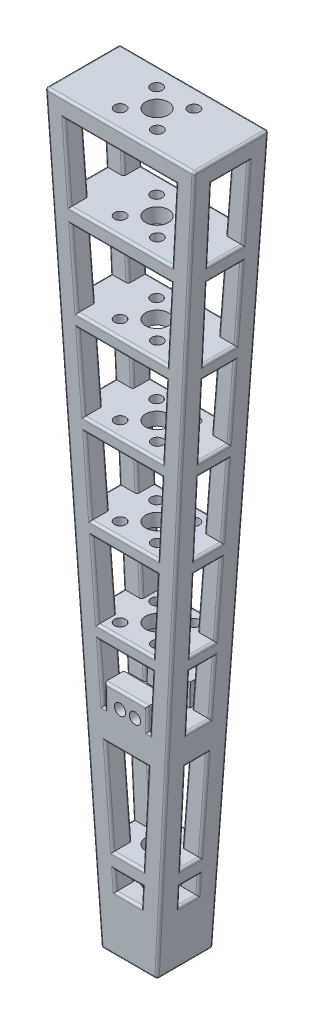
SolidWorks part; units mm, degrees
ref_plane "Płaszczyzna przednia" through (0, 0, 0) normal (0, 0, 1) x (1, 0, 0)
ref_plane "Płaszczyzna górna" through (0, 0, 0) normal (0, 1, 0) x (1, 0, 0)
ref_plane "Płaszczyzna prawa" through (0, 0, 0) normal (1, 0, 0) x (0, 0, -1)
sketch "Szkic1" plane through (0, 0, 0) normal (0, 0, 1) x (1, 0, 0)
  line L0 (0, 0) -> (-15, 0)
  line L1 (-15, 0) -> (-27.5076, 195)
  line L2 (-27.5076, 195) -> (12.4924, 195)
  line L3 (12.4924, 195) -> (0, 0)
  dimension "D1" = 15
  dimension "D2" = 195
  dimension "D3" = 93.67
  dimension "D4" = 40
  dimension "D5" = 93.666
extrude "Dodanie-wyciągnięcie1" add sketch "Szkic1" along normal blind 20
sketch "Szkic5" plane through (0, 0, 0) normal (1, 0, 0) x (0, 0, -1)
  line L0 (-20, 195) -> (-17.5, 0)
  line L1 (-20, 0) -> (0, 0) construction
  line L2 (-17.5, 0) -> (-20, 0)
  line L3 (-20, 0) -> (-20, 195)
  line L4 (0, 195) -> (0, 0)
  line L5 (0, 0) -> (-2.5, 0)
  line L7 (-2.5, 0) -> (0, 195)
  dimension "D1" = 2.5
  dimension "D2" = 2.5
extrude "Wytnij-wyciągnięcie2" cut sketch "Szkic5" against normal blind 232 and the other way blind 103
sketch "Szkic6" plane through (0, 0, 0) normal (0, 0, 1) x (1, 0, 0)
  line L0 (-22.5076, 190) -> (7.4924, 190)
  line L1 (7.4924, 190) -> (-5, 0)
  line L2 (-5, 0) -> (-10, 0)
  line L3 (-10, 0) -> (-22.5076, 190)
  line L4 (12.4924, 195) -> (-27.5076, 195) construction
  line L6 (-21.191, 170) -> (6.1774, 170)
  line L18 (-20.9277, 166) -> (5.9144, 166)
  line L19 (-19.6111, 146) -> (4.5995, 146)
  line L20 (-19.3807, 142.5) -> (4.3693, 142.5)
  line L21 (-18.0641, 122.5) -> (3.0543, 122.5)
  line L22 (-17.8337, 119) -> (2.8242, 119)
  line L23 (-16.5171, 99) -> (1.5092, 99)
  line L24 (-16.2867, 95.5) -> (1.2791, 95.5)
  line L25 (-14.9701, 75.5) -> (-0.0359, 75.5)
  line L26 (-14.7397, 72) -> (-0.266, 72)
  line L27 (-13.7523, 57) -> (-1.2523, 57)
  line L28 (-13.2256, 49) -> (-1.7783, 49)
  line L29 (-3.422, 24) -> (-11.5799, 24)
  line L30 (-11.3166, 20) -> (-3.685, 20)
  line L31 (-10.9874, 15) -> (-4.0138, 15)
  line L32 (-13.2523, 57) -> (-13.2523, 63)
  line L33 (-13.2523, 63) -> (-1.7523, 63)
  line L34 (-1.7523, 63) -> (-1.7523, 57)
  circle A0 centre (-9.1723, 58.6) radius 1.5
  circle A1 centre (-5.1723, 58.6) radius 1.5
  dimension "D48" = 3
  dimension "D49" = 3
  dimension "D1" = 30
  dimension "D2" = 5
  dimension "D3" = 5
  dimension "D4" = 190
  dimension "D5" = 5
  dimension "D6" = 5
  dimension "D7" = 20
  dimension "D8" = 20
  dimension "D9" = 15
  dimension "D10" = 4
  dimension "D11" = 5
  dimension "D22" = 20
  dimension "D23" = 3.5
  dimension "D24" = 20
  dimension "D25" = 3.5
  dimension "D26" = 20
  dimension "D27" = 3.5
  dimension "D28" = 20
  dimension "D29" = 3.5
  dimension "D30" = 15
  dimension "D31" = 8
  dimension "D32" = 25
  dimension "D33" = 4
  dimension "D34" = 5
  dimension "D35" = 0.5
  dimension "D36" = 0.5
  dimension "D37" = 6
  dimension "D38" = 11.5
  dimension "D43" = 1.6
  dimension "D44" = 1.6
  dimension "D45" = 4
  dimension "D46" = 3.42
  dimension "D47" = 4.08
extrude "Wytnij-wyciągnięcie3" cut sketch "Szkic6" against normal blind 93 and the other way blind 71 contours L3 L6 L1 L0 | L3 L19 L1 L18 | L3 L21 L1 L20 | L3 L23 L1 L22 | L3 L25 L1 L24 | L33 L34 L27 L1 L26 L3 L32 | L29 L1 L28 L3 | L3 L31 L1 L30 region at (-7.5072, 180.1529, 0) region at (-7.5062, 156.1718, 0) region at (-7.5053, 132.6955, 0) region at (-7.5043, 109.2268, 0) region at (-7.5034, 85.7699, 0) region at (-7.5027, 67.1069, 0) region at (-7.5015, 37.1991, 0) region at (-7.5007, 17.5375, 0)
sketch "Szkic7" plane through (0, 0, 0) normal (1, 0, 0) x (0, 0, -1)
  line L0 (-15, 190) -> (-5, 190)
  line L1 (-5, 190) -> (-7.5, 15)
  line L2 (-7.5, 15) -> (-12.5, 15)
  line L3 (-12.5, 15) -> (-15, 190)
  line L4 (-20, 195) -> (0, 195) construction
  line L5 (-17.5, 0) -> (-2.5, 0) construction
  line L6 (-14.7143, 170) -> (-5.2857, 170)
  line L19 (-14.6571, 166) -> (-5.3429, 166)
  line L20 (-14.3714, 146) -> (-5.6286, 146)
  line L21 (-14.3214, 142.5) -> (-5.6786, 142.5)
  line L22 (-14.0357, 122.5) -> (-5.9643, 122.5)
  line L23 (-13.9857, 119) -> (-6.0143, 119)
  line L24 (-13.7, 99) -> (-6.3, 99)
  line L25 (-13.65, 95.5) -> (-6.35, 95.5)
  line L26 (-13.3643, 75.5) -> (-6.6357, 75.5)
  line L27 (-13.3143, 72) -> (-6.6857, 72)
  line L28 (-13.1, 57) -> (-6.9, 57)
  line L29 (-12.9857, 49) -> (-7.0143, 49)
  line L30 (-12.6286, 24) -> (-7.3714, 24)
  line L31 (-12.5714, 20) -> (-7.4286, 20)
  point P60 (-10, 49)
  dimension "D1" = 5
  dimension "D2" = 5
  dimension "D3" = 5
  dimension "D4" = 15
  dimension "D5" = 5
  dimension "D6" = 5
  dimension "D7" = 20
  dimension "D8" = 5
  dimension "D9" = 4
  dimension "D21" = 20
  dimension "D22" = 3.5
  dimension "D23" = 20
  dimension "D24" = 3.5
  dimension "D25" = 20
  dimension "D26" = 3.5
  dimension "D27" = 20
  dimension "D28" = 3.5
  dimension "D29" = 15
  dimension "D30" = 8
  dimension "D31" = 25
  dimension "D32" = 24
  dimension "D33" = 4
extrude "Wytnij-wyciągnięcie7" cut sketch "Szkic7" against normal blind 403 and the other way blind 244 contours L3 L6 L1 L0 | L3 L20 L1 L19 | L3 L22 L1 L21 | L3 L24 L1 L23 | L3 L26 L1 L25 | L3 L28 L1 L27 | L30 L1 L29 L3 | L31 L3 L2 L1 region at (0, 180.098, 10) region at (0, 156.1055, 10) region at (0, 132.614, 10) region at (0, 109.1239, 10) region at (0, 85.6358, 10) region at (0, 64.5835, 10) region at (0, 36.7651, 10) region at (0, 17.5117, 10)
sketch "Szkic8" plane through (0, 0, 0) normal (0, 1, 0) x (1, 0, 0)
  line L0 (12.4924, -20) -> (-27.5076, -20) construction
  line L2 (-27.5076, -20) -> (-27.5076, 0) construction
  circle A0 centre (-12.5076, -5.1) radius 1.5
  circle A1 centre (-2.5076, -5.1) radius 1.5
  circle A2 centre (-2.5076, -14.9) radius 1.5
  circle A3 centre (-12.5076, -14.9) radius 1.5
  circle A4 centre (-7.5076, -10) radius 3.05
  dimension "D1" = 3
  dimension "D2" = 3
  dimension "D3" = 3
  dimension "D4" = 3
  dimension "D9" = 6.1
  dimension "D5" = 4.9
  dimension "D6" = 4.9
  dimension "D7" = 20
  dimension "D8" = 10
  dimension "D10" = 4.9
  dimension "D11" = 4.9
  dimension "D12" = 5
  dimension "D13" = 5
  dimension "D14" = 5
  dimension "D15" = 15
fillet "Zaokrąglenie5" radius 0.6 148 edges at (9.3533, 146, 10) (9.994, 156, 5.4857) (7.6236, 119, 10) (6.983, 109, 13.8429) (3.6516, 57, 10) (4.1321, 64.5, 6.7929) (4.6126, 72, 10) (2.3383, 36.5, 7.1929) (2.3383, 36.5, 12.8071) (12.4924, 195, 10) (0, 0, 10) (11.5315, 180, 5.1429) (12.1721, 190, 10) (11.5315, 180, 14.8571) (10.8908, 170, 10) (1.1211, 17.5, 12.5357) (0.961, 15, 10) (1.1211, 17.5, 7.4643) (4.8368, 75.5, 10) (5.4775, 85.5, 6.4929) (6.1181, 95.5, 10) (7.8478, 122.5, 10) (8.4885, 132.5, 5.8214) (9.1291, 142.5, 10) (5.257, 156, 19.5) (-7.5066, 166, 19.6282) (-20.2694, 156, 19.5) (-7.5058, 146, 19.3718) (3.7118, 132.5, 19.1987) (-7.5057, 142.5, 19.3269) (-18.7224, 132.5, 19.1987) (-7.5049, 122.5, 19.0705) (2.1667, 109, 18.8974) (-7.5047, 119, 19.0256) (-17.1754, 109, 18.8974) (-7.5039, 99, 18.7692) (0.6216, 85.5, 18.5962) (-7.5038, 95.5, 18.7244) (-15.6284, 85.5, 18.5962) (-7.503, 75.5, 18.4679) (-7.5023, 63, 18.3077) (-1.7523, 60, 18.2692) (-1.5023, 57, 18.2308) (-0.7591, 64.5, 18.3269) (-7.5029, 72, 18.4231) (-14.246, 64.5, 18.3269) (-13.5023, 57, 18.2308) (-13.2523, 60, 18.2692) (-3.8494, 17.5, 17.7244) (-7.5008, 20, 17.7564) (-11.152, 17.5, 17.7244) (-7.5006, 15, 17.6923) (-7.5, 0, 17.5) (-7.5076, 195, 20) (6.2462, 97.5, 18.75) (-7.5068, 170, 19.6795) (6.8349, 180, 19.8077) (-7.5076, 190, 19.9359) (-21.8493, 180, 19.8077) (-7.501, 24, 17.8077) (-2.6001, 36.5, 17.9679) (-7.5019, 49, 18.1282) (-12.4028, 36.5, 17.9679) (-25.6475, 166, 10) (-25.006, 156, 5.4857) (-22.6328, 119, 10) (-21.9914, 109, 6.1571) (-21.35, 99, 10) (-21.9914, 109, 13.8429) (-19.1371, 64.5, 6.7929) (-16.5394, 24, 10) (-17.3412, 36.5, 12.8071) (-15, 0, 10) (-27.5076, 195, 10) (-21.2538, 97.5, 18.75) (-26.5454, 180, 5.1429) (-25.904, 170, 10) (-26.5454, 180, 14.8571) (-27.1869, 190, 10) (-16.1225, 17.5, 7.4643) (-15.9621, 15, 10) (-16.1225, 17.5, 12.5357) (-16.2828, 20, 10) (-20.4841, 85.5, 6.4929) (-19.8427, 75.5, 10) (-20.4841, 85.5, 13.5071) (-24.1401, 142.5, 10) (-23.4987, 132.5, 5.8214) (5.257, 156, 0.5) (-7.5058, 146, 0.6282) (-20.2694, 156, 0.5) (-7.5066, 166, 0.3718) (3.7118, 132.5, 0.8013) (-7.5049, 122.5, 0.9295) (-18.7224, 132.5, 0.8013) (-7.5057, 142.5, 0.6731) (2.1667, 109, 1.1026) (-7.5039, 99, 1.2308) (-17.1754, 109, 1.1026) (-7.5047, 119, 0.9744) (0.6216, 85.5, 1.4038) (-7.503, 75.5, 1.5321) (-15.6284, 85.5, 1.4038) (-7.5038, 95.5, 1.2756) (-13.5023, 57, 1.7692) (-14.246, 64.5, 1.6731) (-7.5029, 72, 1.5769) (-0.7591, 64.5, 1.6731) (-1.5023, 57, 1.7692) (-1.7523, 60, 1.7308) (-7.5023, 63, 1.6923) (-13.2523, 60, 1.7308) (-3.8494, 17.5, 2.2756) (-7.5006, 15, 2.3077) (-11.152, 17.5, 2.2756) (-7.5008, 20, 2.2436) (-7.5076, 195, 0) (-21.2538, 97.5, 1.25) (-7.5, 0, 2.5) (6.2462, 97.5, 1.25) (-7.5076, 190, 0.0641) (6.8349, 180, 0.1923) (-7.5068, 170, 0.3205) (-21.8493, 180, 0.1923) (-12.4028, 36.5, 2.0321) (-7.5019, 49, 1.8718) (-2.6001, 36.5, 2.0321) (-7.501, 24, 2.1923) (5.4775, 85.5, 13.5071) (8.4885, 132.5, 14.1786) (3.1391, 49, 10) (10.6346, 166, 10) (9.994, 156, 14.5143) (6.3423, 99, 10) (6.983, 109, 6.1571) (4.1321, 64.5, 13.2071) (-21.1255, 95.5, 10) (-22.8573, 122.5, 10) (-23.4987, 132.5, 14.1786) (-18.1429, 49, 10) (-24.3646, 146, 10) (-25.006, 156, 14.5143) (-19.6182, 72, 10) (-18.6561, 57, 10) (-19.1371, 64.5, 13.2071) (1.5375, 24, 10) (1.2813, 20, 10) (-17.3412, 36.5, 7.1929)
extrude "Wytnij-wyciągnięcie8" cut sketch "Szkic8" against normal blind 21 and the other way blind 270 contours A4 region at (-7.5076, 0, 10)
extrude "Wytnij-wyciągnięcie10" cut sketch "Szkic8<4>" against normal blind 124 from surface starting at face at (-7.5076, 195, 6.95)
sketch "Szkic8<4>" plane through (0, 0, 0) normal (0, 1, 0) x (1, 0, 0) same geometry as "Szkic8"
fillet "Zaokrąglenie7" radius 0.6 32 edges at (6.8349, 180, 5.1429) (5.257, 156, 5.4857) (3.7118, 132.5, 5.8214) (2.1667, 109, 6.1571) (0.6216, 85.5, 6.4929) (-0.7591, 64.5, 6.7929) (-2.6001, 36.5, 7.1929) (-3.8494, 17.5, 7.4643) (-11.152, 17.5, 7.4643) (-12.4028, 36.5, 7.1929) (-14.246, 64.5, 6.7929) (-15.6284, 85.5, 6.4929) (-17.1754, 109, 6.1571) (-18.7224, 132.5, 5.8214) (-20.2694, 156, 5.4857) (-21.8493, 180, 5.1429) (-21.8493, 180, 14.8571) (-20.2694, 156, 14.5143) (-18.7224, 132.5, 14.1786) (-17.1754, 109, 13.8429) (-15.6284, 85.5, 13.5071) (-14.246, 64.5, 13.2071) (-12.4028, 36.5, 12.8071) (-11.152, 17.5, 12.5357) (-3.8494, 17.5, 12.5357) (-2.6001, 36.5, 12.8071) (-0.7591, 64.5, 13.2071) (0.6216, 85.5, 13.5071) (2.1667, 109, 13.8429) (3.7118, 132.5, 14.1786) (5.257, 156, 14.5143) (6.8349, 180, 14.8571)
extrude "Wytnij-wyciągnięcie11" cut sketch "Szkic6<10>" against normal blind 20 and the other way blind 42 contours A1 | A0 | A0 | A1 region at (-9.1723, 58.6, 0) region at (-5.1723, 58.6, 0)
sketch "Szkic6<10>" plane through (0, 0, 0) normal (0, 0, 1) x (1, 0, 0) same geometry as "Szkic6"
